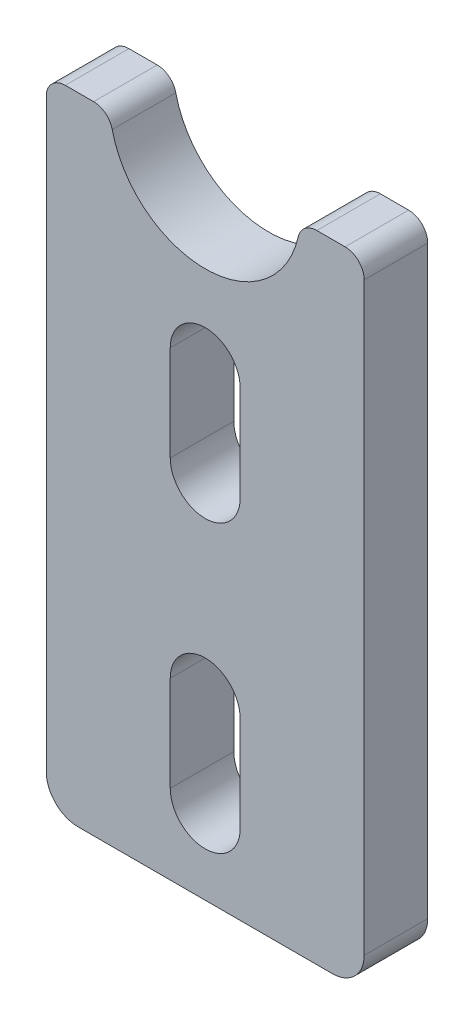
SolidWorks part; units mm, degrees
note: The reader was unsure of these and kept them because the rebuilt part matched: thickness of "Taban-Flanş1", "Sac-Levha1", "Sac-Levha2", "Sac-Levha3".
material "1.4003 (X2CrNi12)"
ref_plane "Ön Düzlem" through (0, 0, 0) normal (0, 0, 1) x (1, 0, 0)
ref_plane "Üst Düzlem" through (0, 0, 0) normal (0, 1, 0) x (1, 0, 0)
ref_plane "Sağ Düzlem" through (0, 0, 0) normal (1, 0, 0) x (0, 0, -1)
sketch "Çizim1" plane through (0, 0, 0) normal (0, 0, 1) x (1, 0, 0)
  line L1 (-25, 50) -> (25, 50)
  line L2 (-25, 50) -> (-25, -50)
  line L3 (-25, -50) -> (25, -50)
  line L4 (25, 50) -> (25, -50)
  line L5 (-25, 50) -> (25, -50) construction
  line L6 (-25, -50) -> (25, 50) construction
  point P0 (0, 0)
  dimension "D1" = 100
  dimension "D2" = 50
base flange "Taban-Flanş1" sketch "Çizim1" thickness 10 reverse thickness direction no parameters "D1"=5
sketch "Çizim6" plane through (0, 0, 0) normal (0, 0, 1) x (1, 0, 0)
  line L0 (0, 22.5) -> (0, 7.5) construction
  line L1 (5.5, 22.5) -> (5.5, 7.5)
  line L2 (-5.5, 22.5) -> (-5.5, 7.5)
  line L4 (0, -37.5) -> (0, -22.5) construction
  line L5 (-5.5, -37.5) -> (-5.5, -22.5)
  line L6 (5.5, -37.5) -> (5.5, -22.5)
  arc A0 (5.5, 22.5) -> (-5.5, 22.5) centre (0, 22.5) ccw
  arc A1 (-5.5, 7.5) -> (5.5, 7.5) centre (0, 7.5) ccw
  arc A2 (-5.5, -37.5) -> (5.5, -37.5) centre (0, -37.5) ccw
  arc A3 (5.5, -22.5) -> (-5.5, -22.5) centre (0, -22.5) ccw
  point P3 (0, 15)
  point P12 (0, -30)
  dimension "D1" = 5.5
  dimension "D4" = 5.5
  dimension "D2" = 15
  dimension "D3" = 30
  dimension "D5" = 15
  dimension "D6" = 15
extrude "Kes-Ekstrüzyon1" cut sketch "Çizim6" against normal blind 20
fillet "Radyus1" radius 5 2 edges at (25, -50, -5) (-25, -50, -5)
sketch "Çizim7" plane through (0, 0, 0) normal (0, 0, 1) x (1, 0, 0)
  line L1 (25, 50) -> (-25, 50) construction
  circle A1 centre (0, 51) radius 15
  dimension "D1" = 30
  dimension "D2" = 1
extrude "Kes-Ekstrüzyon2" cut sketch "Çizim7" against normal blind 10
fillet "Radyus2" radius 3 4 edges at (25, 50, -5) (-14.9666, 50, -5) (14.9666, 50, -5) (-25, 50, -5)
sketch "Büküm-Çizgileri1" [suppressed] plane through (0, 0, 0) normal (0, 1, 0) x (1, 0, 0)
sketch "Sınırlandırma-Kutusu1" [suppressed] plane through (0, 0, 0) normal (0, 1, 0) x (1, 0, 0)
sheet metal parameters "Sac-Levha1" thickness 10 parameters "D1"=5
flat pattern "Düz-Çoğaltma1" [suppressed]
sketch "Büküm-Çizgileri2" plane through (0, 0, 0) normal (0, 1, 0) x (1, 0, 0)
sketch3d "Sınırlandırma-Kutusu2" [suppressed]
  line L0 (-20, 70, 0) -> (-20, -70, 0) construction
  line L1 (20, 70, 0) -> (20, -70, 0) construction
  line L2 (-20, 70, 0) -> (20, 70, 0) construction
  line L3 (-20, -70, 0) -> (20, -70, 0) construction
sheet metal parameters "Sac-Levha2" thickness 10 parameters "D1"=5, "D7"=5
flat pattern "Düz-Çoğaltma1"
sketch "Büküm-Çizgileri2" plane through (0, 0, 0) normal (0, 1, 0) x (1, 0, 0)
sketch3d "Sınırlandırma-Kutusu2" [suppressed]
  line L0 (20, -85, 0) -> (20, 85, 0) construction
  line L1 (-20, -85, 0) -> (-20, 85, 0) construction
  line L2 (20, -85, 0) -> (-20, -85, 0) construction
  line L3 (20, 85, 0) -> (-20, 85, 0) construction
sheet metal parameters "Sac-Levha3" thickness 10 parameters "D1"=5, "D7"=5
flat pattern "Düz-Çoğaltma1"
sketch "Büküm-Çizgileri2" plane through (0, 0, 0) normal (0, 1, 0) x (1, 0, 0)
sketch3d "Sınırlandırma-Kutusu2" [suppressed]
  line L0 (25, -50, 0) -> (25, 50, 0) construction
  line L1 (-25, -50, 0) -> (-25, 50, 0) construction
  line L2 (25, -50, 0) -> (-25, -50, 0) construction
  line L3 (25, 50, 0) -> (-25, 50, 0) construction
